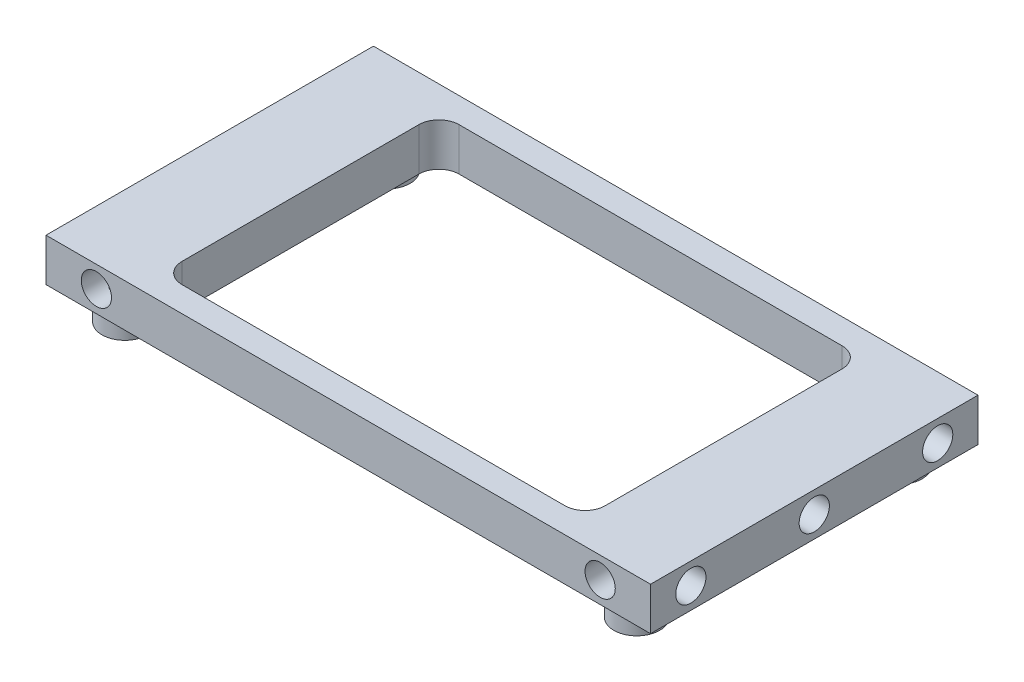
SolidWorks part; units mm, degrees
ref_plane "Front Plane" through (0, 0, 0) normal (0, 0, 1) x (1, 0, 0)
ref_plane "Top Plane" through (0, 0, 0) normal (0, 1, 0) x (1, 0, 0)
ref_plane "Right Plane" through (0, 0, 0) normal (1, 0, 0) x (0, 0, -1)
sketch "Sketch1" plane through (0, 0, 0) normal (1, 0, 0) x (0, 0, -1)
  line L1 (-32.5, -4.25) -> (32.5, -4.25)
  line L2 (-32.5, -4.25) -> (-32.5, 4.25)
  line L3 (-32.5, 4.25) -> (32.5, 4.25)
  line L4 (32.5, -4.25) -> (32.5, 4.25)
  line L5 (-32.5, -4.25) -> (32.5, 4.25) construction
  line L6 (-32.5, 4.25) -> (32.5, -4.25) construction
  point P0 (0, 0)
  dimension "D1" = 8.5
  dimension "D2" = 65
extrude "Boss-Extrude1" add sketch "Sketch1" along normal blind 120
hole_wizard "Ø6.0mm Dowel Hole1" positions "Sketch2" profile "Sketch3" hole size "Ø6.0" standard "ANSI Metric"
sketch "Sketch2" plane through (120, 0, 0) normal (1, 0, 0) x (0, 0, -1)
  line L0 (-32.5, 4.25) -> (-32.5, -4.25) construction
  line L1 (32.5, -4.25) -> (32.5, 4.25) construction
  point P0 (-24.5, 0)
  point P2 (0, 0)
  point P5 (24.5, 0)
  dimension "D1" = 8
  dimension "D2" = 8
sketch "Sketch3" plane through (120, 0, 24.5) normal (0, 1, 0) x (0, 0, -1)
  line L0 (0, 0) -> (0, 11.8026)
  line L1 (0, 11.8026) -> (3, 10)
  line L2 (3, 10) -> (3, 0)
  line L5 (3, 0) -> (0, 0)
  line L10 (0, 11.8026) -> (-3, 10) construction
  line L11 (0, -6.35) -> (0, 107.95) construction
  dimension "Hole Dia." = 6
  dimension "Hole Depth" = 10
  dimension "Drill Angle" = 118
ref_plane "Plane1" through (60, 0, 0) normal (1, 0, 0) x (0, 0, -1)
mirror "Mirror1" about plane through (60, 0, 0) normal (1, 0, 0) of "Ø6.0mm Dowel Hole1"
hole_wizard "Ø6.0mm Dowel Hole2" positions "Sketch4" profile "Sketch5" hole size "Ø6.0" standard "ANSI Metric"
sketch "Sketch4" plane through (0, 0, -32.5) normal (0, 0, -1) x (-1, 0, 0)
  line L0 (-120, -4.25) -> (-120, 4.25) construction
  line L1 (0, -4.25) -> (0, 4.25) construction
  line L2 (-120, 0) -> (0, 0) construction
  point P0 (-110, 0)
  point P2 (-10, 0)
  dimension "D1" = 10
  dimension "D2" = 10
sketch "Sketch5" plane through (110, 0, -32.5) normal (1, 0, 0) x (0, 1, 0)
  line L0 (0, 0) -> (0, 9.8026)
  line L1 (0, 9.8026) -> (3, 8)
  line L2 (3, 8) -> (3, 0)
  line L5 (3, 0) -> (0, 0)
  line L10 (0, 9.8026) -> (-3, 8) construction
  line L11 (0, -6.35) -> (0, 107.95) construction
  dimension "Hole Dia." = 6
  dimension "Hole Depth" = 8
  dimension "Drill Angle" = 118
mirror "Mirror2" about plane through (0, 0, 0) normal (0, 0, 1) of "Ø6.0mm Dowel Hole2"
sketch "Sketch6" plane through (0, 4.25, 0) normal (0, 1, 0) x (1, 0, 0)
  line L0 (86, -7) -> (86, 7) construction
  line L1 (80, -7) -> (80, 7)
  line L2 (92, -7) -> (92, 7)
  line L3 (120, 32.5) -> (120, -32.5) construction
  arc A0 (80, -7) -> (92, -7) centre (86, -7) ccw
  arc A1 (92, 7) -> (80, 7) centre (86, 7) ccw
  point P2 (86, 0)
  point P10 (120, 0)
  dimension "D3" = 12
  dimension "D1" = 40
  dimension "D2" = 14
extrude "Cut-Extrude1" cut sketch "Sketch6" against normal through all
mirror "Mirror3" about plane through (60, 0, 0) normal (1, 0, 0) of "Cut-Extrude1"
sketch "Sketch7" plane through (0, 4.25, 0) normal (0, 1, 0) x (1, 0, 0)
  line L0 (120, 32.5) -> (0, 32.5) construction
  line L1 (87, 17) -> (33, 17)
  line L2 (87, 17) -> (87, -17)
  line L3 (87, -17) -> (33, -17)
  line L4 (33, 17) -> (33, -17)
  line L5 (87, 17) -> (33, -17) construction
  line L6 (87, -17) -> (33, 17) construction
  point P0 (60, 0)
  point P8 (60, 32.5)
  dimension "D1" = 54
  dimension "D2" = 34
hole_wizard "Ø3.0mm Dowel Hole1" positions "Sketch8" profile "Sketch9" hole size "Ø3.0" standard "ANSI Metric" end condition through all
sketch "Sketch8" plane through (0, 4.25, 0) normal (0, 1, 0) x (1, 0, 0)
  line L0 (120, -32.5) -> (0, -32.5) construction
  line L1 (120, 32.5) -> (0, 32.5) construction
  line L2 (120, 32.5) -> (120, -32.5) construction
  line L3 (0, 32.5) -> (0, -32.5) construction
  point P0 (87, -17)
  point P3 (87, 17)
  point P6 (33, 17)
  point P9 (33, -17)
  point P13 (100, -24.5)
  point P15 (60, -24.5)
  point P17 (20, -24.5)
  point P19 (100, 24.5)
  point P21 (60, 24.5)
  point P23 (20, 24.5)
  point P40 (60, 32.5)
  dimension "D1" = 8
  dimension "D2" = 8
  dimension "D3" = 20
  dimension "D4" = 20
sketch "Sketch9" plane through (87, 4.25, 17) normal (1, 0, 0) x (0, 0, 1)
  line L0 (0, 0) -> (0, 8.5)
  line L1 (0, 8.5) -> (1.75, 8.5)
  line L2 (1.75, 8.5) -> (1.75, 0)
  line L5 (1.75, 0) -> (0, 0)
  line L11 (0, -6.35) -> (0, 107.95) construction
  dimension "Thru Hole Dia." = 3.5
  dimension "Thru Hole Depth" = 8.5
sketch "Sketch10" plane through (0, -4.25, 0) normal (0, -1, 0) x (1, 0, 0)
  line L0 (120, 32.5) -> (0, 32.5) construction
  line L1 (40, -21.5) -> (80, -21.5)
  line L2 (40, -21.5) -> (40, 21.5)
  line L3 (40, 21.5) -> (80, 21.5)
  line L4 (80, -21.5) -> (80, 21.5)
  line L5 (40, -21.5) -> (80, 21.5) construction
  line L6 (40, 21.5) -> (80, -21.5) construction
  line L7 (0, 32.5) -> (0, -32.5) construction
  line L8 (40, 21.5) -> (34, 13)
  line L9 (34, -13) -> (40, -21.5)
  line L10 (40, -7) -> (40, 7) construction
  line L11 (80, 21.5) -> (86, 13)
  line L12 (86, -13) -> (80, -21.5)
  arc A0 (40, 7) -> (28, 7) centre (34, 7) ccw construction
  arc A1 (28, -7) -> (40, -7) centre (34, -7) ccw construction
  arc A2 (28, -7) -> (40, -7) centre (34, -7) ccw
  arc A3 (40, 7) -> (28, 7) centre (34, 7) ccw
  arc A4 (80, -7) -> (92, -7) centre (86, -7) ccw construction
  arc A5 (92, 7) -> (80, 7) centre (86, 7) ccw construction
  arc A6 (80, -7) -> (92, -7) centre (86, -7) ccw
  arc A7 (92, 7) -> (80, 7) centre (86, 7) ccw
  point P0 (60, 0)
  point P7 (60, 32.5)
  point P11 (0, 0)
  line M17 (80, -7) -> (80, 7)
  arc M18 (80, 7) -> (92, 7) centre (86, 7) cw
  arc M20 (92, -7) -> (80, -7) centre (86, -7) cw
  arc M21 (28, 7) -> (40, 7) centre (34, 7) cw
  line M22 (40, 7) -> (40, -7)
  arc M23 (40, -7) -> (28, -7) centre (34, -7) cw
  dimension "D1" = 43
extrude "Cut-Extrude2" cut sketch "Sketch10" against normal through all contours L2 L8 M21 | L1 L4 L3 L2 M17 M22 | L9 L2 M23 | L11 L4 M18 | L12 L4 M20 region at (60, -4.25, 0) region at (38.1534, -4.25, -14.8629) region at (81.8466, -4.25, -14.8629) region at (38.1534, -4.25, 14.8629) region at (81.8466, -4.25, 14.8629)
fillet "Fillet1" radius 6 8 edges at (34, 0, -13) (40, 0, -21.5) (34, 0, 13) (40, 0, 21.5) (80, 0, -21.5) (86, 0, -13) (80, 0, 21.5) (86, 0, 13)
sketch "Sketch11" plane through (0, -4.25, 0) normal (0, -1, 0) x (1, 0, 0)
  line L0 (120, 32.5) -> (0, 32.5) construction
  line L1 (110.8, -26.035) -> (9.2, -26.035)
  line L2 (110.8, -26.035) -> (110.8, 26.035)
  line L3 (110.8, 26.035) -> (9.2, 26.035)
  line L4 (9.2, -26.035) -> (9.2, 26.035)
  line L5 (110.8, -26.035) -> (9.2, 26.035) construction
  line L6 (110.8, 26.035) -> (9.2, -26.035) construction
  line L7 (120, 32.5) -> (120, -32.5) construction
  circle A0 centre (9.2, 26.035) radius 2.55
  circle A1 centre (110.8, 26.035) radius 2.55
  circle A2 centre (110.8, -26.035) radius 2.55
  circle A3 centre (9.2, -26.035) radius 2.55
  circle A4 centre (9.2, 26.035) radius 4.55
  circle A5 centre (110.8, 26.035) radius 4.55
  circle A6 centre (110.8, -26.035) radius 4.55
  circle A7 centre (9.2, -26.035) radius 4.55
  point P0 (60, 0)
  point P11 (60, 32.5)
  point P14 (120, 0)
  dimension "D1" = 5.1
  dimension "D4" = 2
  dimension "D2" = 101.6
  dimension "D3" = 52.07
extrude "Boss-Extrude2" add sketch "Sketch11" along normal blind 5 contours L4 A7 L1 A3 | L1 A7 L4 A3 | L3 A4 L4 A0 | L4 A4 L3 A0 | L2 A5 L3 A1 | L3 A5 L2 A1 | L2 A6 L1 A2 | L1 A6 L2 A2 region at (6.0737, -4.25, -29.1613) region at (11.5198, -4.25, -23.7152) region at (108.4802, -4.25, -23.7152) region at (107.25, -4.25, -26.1637) region at (6.0737, -4.25, 29.1613) region at (11.5198, -4.25, 23.7152) region at (108.4802, -4.25, 23.7152) region at (110.9287, -4.25, 22.485)
sketch "Sketch12" plane through (0, -4.25, 0) normal (0, -1, 0) x (1, 0, 0)
  circle A0 centre (110.8, -26.035) radius 2.55 construction
  circle A1 centre (110.8, 26.035) radius 2.55 construction
  circle A2 centre (9.2, 26.035) radius 2.55 construction
  circle A3 centre (9.2, -26.035) radius 2.55 construction
  circle A4 centre (110.8, -26.035) radius 2.55
  circle A5 centre (110.8, 26.035) radius 2.55
  circle A6 centre (9.2, 26.035) radius 2.55
  circle A7 centre (9.2, -26.035) radius 2.55
extrude "Cut-Extrude3" cut sketch "Sketch12" against normal blind 1.7
chamfer "Chamfer1" distance 1.5 angle 45 4 edges at (9.2, -4.25, -21.485) (110.8, -4.25, -21.485) (110.8, -4.25, 30.585) (9.2, -4.25, 30.585)
sketch "Sketch13" plane through (0, -4.25, 0) normal (0, -1, 0) x (1, 0, 0)
  line L0 (120, 32.5) -> (0, 32.5) construction
  line L1 (102, -27.5) -> (18, -27.5)
  line L2 (102, -27.5) -> (102, 27.5)
  line L3 (102, 27.5) -> (18, 27.5)
  line L4 (18, -27.5) -> (18, 27.5)
  line L5 (102, -27.5) -> (18, 27.5) construction
  line L6 (102, 27.5) -> (18, -27.5) construction
  line L7 (120, 32.5) -> (120, -32.5) construction
  point P0 (60, 0)
  point P7 (60, 32.5)
  point P10 (120, 0)
  dimension "D1" = 84
  dimension "D2" = 55
extrude "Cut-Extrude4" cut sketch "Sketch13" against normal through all
fillet "Fillet2" radius 4 4 edges at (102, 0, -27.5) (18, 0, -27.5) (18, 0, 27.5) (102, 0, 27.5)
